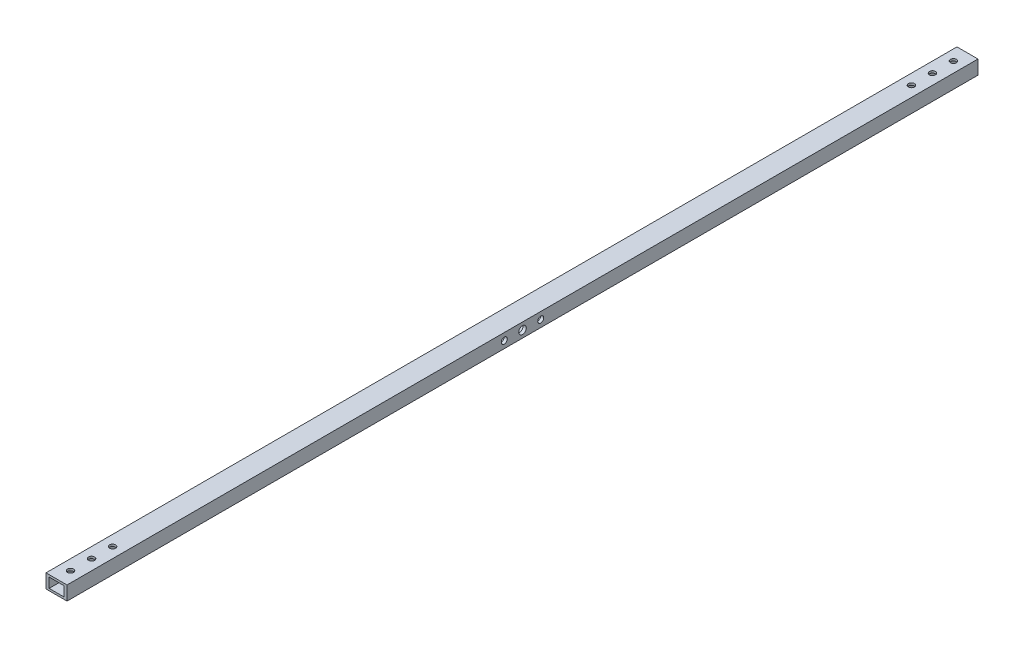
SolidWorks part; units mm, degrees
material "PC 高粘度"
ref_plane "前视基准面" through (0, 0, 0) normal (0, 0, 1) x (1, 0, 0)
ref_plane "上视基准面" through (0, 0, 0) normal (0, 1, 0) x (1, 0, 0)
ref_plane "右视基准面" through (0, 0, 0) normal (1, 0, 0) x (0, 0, -1)
other "Configuration Table"
sketch "草图1" plane through (0, 0, 0) normal (0, 0, 1) x (1, 0, 0)
  line L1 (-7.5, 5) -> (7.5, 5)
  line L2 (-7.5, 5) -> (-7.5, -5)
  line L3 (-7.5, -5) -> (7.5, -5)
  line L4 (7.5, 5) -> (7.5, -5)
  line L5 (-7.5, 5) -> (7.5, -5) construction
  line L6 (-7.5, -5) -> (7.5, 5) construction
  line L7 (-5.25, 3.5) -> (5.25, 3.5)
  line L8 (-5.25, 3.5) -> (-5.25, -3.5)
  line L9 (-5.25, -3.5) -> (5.25, -3.5)
  line L10 (5.25, 3.5) -> (5.25, -3.5)
  line L11 (-5.25, 3.5) -> (5.25, -3.5) construction
  line L12 (-5.25, -3.5) -> (5.25, 3.5) construction
  point P0 (0, 0)
  point P5 (0, 0)
  dimension "D1" = 10
  dimension "D2" = 1.5
  dimension "D3" = 15
extrude "凸台-拉伸1" add sketch "草图1" along normal blind 650
sketch "草图2" plane through (0, -5, 0) normal (0, -1, 0) x (1, 0, 0)
  line L4 (-7.5, 0) -> (7.5, 0)
  line L5 (7.5, 0) -> (7.5, 650)
  line L6 (7.5, 650) -> (-7.5, 650)
  line L7 (-7.5, 650) -> (-7.5, 0)
  line L8 (-7.5, 0) -> (7.5, 0)
  line L9 (7.5, 0) -> (7.5, 650)
  line L10 (7.5, 650) -> (-7.5, 650)
  line L11 (-7.5, 650) -> (-7.5, 0)
  circle A0 centre (0, 640) radius 2.15 construction
  circle A1 centre (0, 625) radius 2.15 construction
  circle A2 centre (0, 610) radius 2.15 construction
  circle A3 centre (0, 40) radius 2.15 construction
  circle A4 centre (0, 25) radius 2.15 construction
  circle A5 centre (0, 10) radius 2.15 construction
  circle A6 centre (0, 640) radius 2.15
  circle A7 centre (0, 625) radius 2.15
  circle A8 centre (0, 610) radius 2.15
  circle A9 centre (0, 40) radius 2.15
  circle A10 centre (0, 25) radius 2.15
  circle A11 centre (0, 10) radius 2.15
  dimension "D1" = 0
extrude "切除-拉伸1" cut sketch "草图2" against normal through all contours A6 | A7 | A8 | A11 | A10 | A9 region at (0, -5, 640) region at (0, -5, 625) region at (0, -5, 610) region at (0, -5, 40) region at (0, -5, 25) region at (0, -5, 10)
sketch "草图3" plane through (7.5, 0, 0) normal (1, 0, 0) x (0, 0, -1)
  circle A0 centre (-338, 0) radius 2.15 construction
  circle A1 centre (-312, 0) radius 2.15 construction
  circle A2 centre (-338, 0) radius 2.15
  circle A3 centre (-312, 0) radius 2.15
  circle A4 centre (-325, 0) radius 2.7 construction
  circle A5 centre (-325, 0) radius 2.7
extrude "切除-拉伸2" cut sketch "草图3" against normal through all
